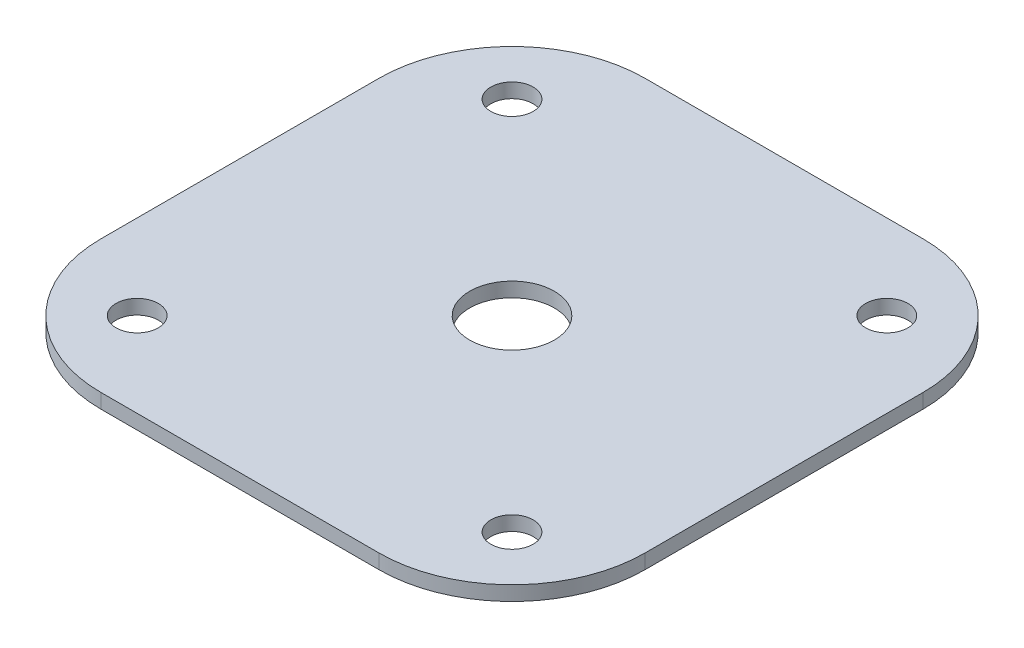
SolidWorks part; units mm, degrees
ref_plane "Front Plane" through (0, 0, 0) normal (0, 0, 1) x (1, 0, 0)
ref_plane "Top Plane" through (0, 0, 0) normal (0, 1, 0) x (1, 0, 0)
ref_plane "Right Plane" through (0, 0, 0) normal (1, 0, 0) x (0, 0, -1)
sketch "Sketch1" plane through (0, 0, 0) normal (0, 1, 0) x (1, 0, 0)
  line L0 (0, 0) -> (0, 22.5) construction
  line L1 (-11.5, 22.5) -> (11.5, 22.5)
  line L2 (-22.5, 11.5) -> (-22.5, -11.5)
  line L3 (-11.5, -22.5) -> (11.5, -22.5)
  line L4 (22.5, 11.5) -> (22.5, -11.5)
  line L5 (0, 0) -> (-22.5, 0) construction
  line L6 (0, 0) -> (-11.5, 11.5) construction
  line L7 (0, 0) -> (11.5, 11.5) construction
  circle A0 centre (0, 0) radius 3.5
  arc A1 (-22.5, -11.5) -> (-11.5, -22.5) centre (-11.5, -11.5) ccw
  arc A2 (11.5, -22.5) -> (22.5, -11.5) centre (11.5, -11.5) ccw
  arc A3 (11.5, 22.5) -> (22.5, 11.5) centre (11.5, 11.5) cw
  arc A4 (-11.5, 22.5) -> (-22.5, 11.5) centre (-11.5, 11.5) ccw
  circle A5 centre (0, 0) radius 21.9203 construction
  circle A6 centre (-15.5, 15.5) radius 1.75
  circle A7 centre (15.5, 15.5) radius 1.75
  circle A8 centre (15.5, -15.5) radius 1.75
  circle A9 centre (-15.5, -15.5) radius 1.75
  dimension "D1" = 7
  dimension "D4" = 11
  dimension "D5" = 3.5
  dimension "D6" = 31
  dimension "D2" = 45
  dimension "D3" = 45
extrude "Boss-Extrude1" add sketch "Sketch1" along normal blind 1.2
sketch "Sketch2" plane through (0, 0, 0) normal (0, 1, 0) x (1, 0, 0)
  line L0 (-22.5, 11.5) -> (-22.5, -11.5) construction
  line L3 (-12.1262, 5) -> (-44, 5)
  line L4 (-12.1262, 5) -> (-12.1262, -5)
  line L5 (-12.1262, -5) -> (-44, -5)
  line L6 (-46, 3) -> (-46, -3)
  arc A3 (-44, -5) -> (-46, -3) centre (-44, -3) cw
  arc A4 (-44, 5) -> (-46, 3) centre (-44, 3) ccw
  point P5 (-12.1262, 0)
  dimension "D2" = 2
  dimension "D1" = 10
  dimension "D3" = 23.5
extrude "Boss-Extrude2" [suppressed] add sketch "Sketch2" along normal up to surface (1.2 mm away) up to face at (15.5, 1.2, 13.75)
fillet "Fillet1" [suppressed] radius 2
